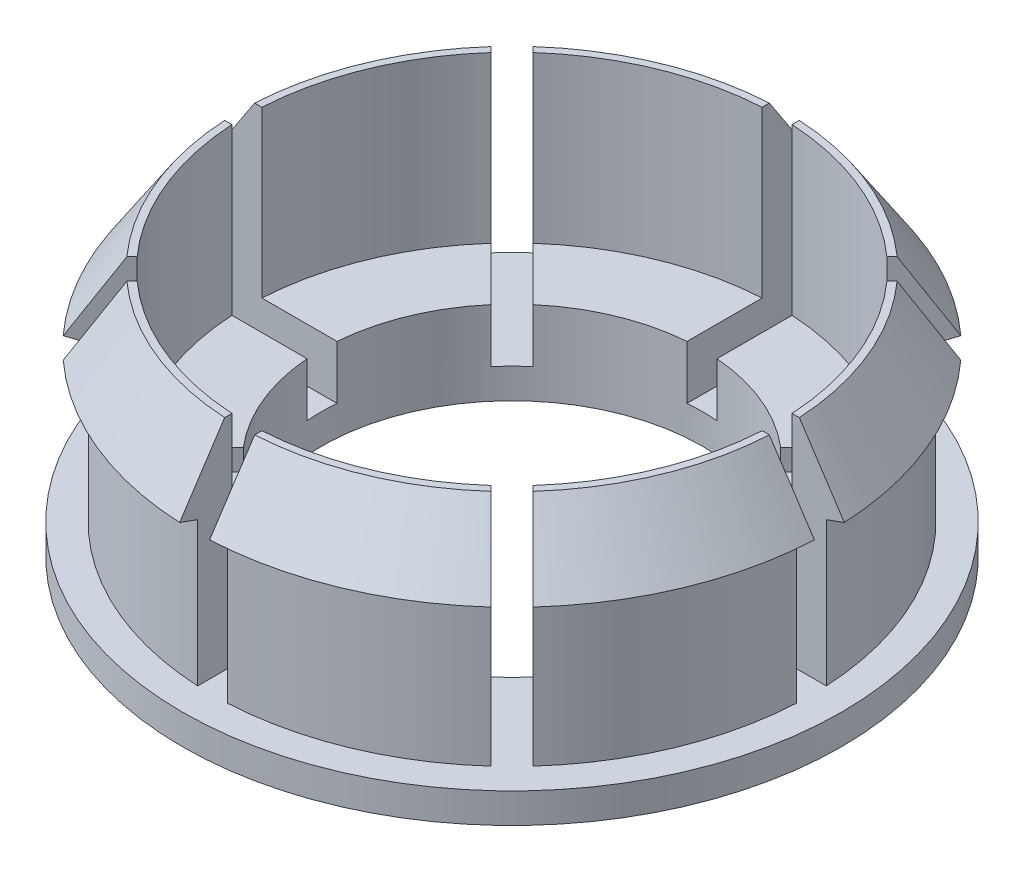
SolidWorks part; units mm, degrees
ref_plane "Front Plane" through (0, 0, 0) normal (0, 0, 1) x (1, 0, 0)
ref_plane "Top Plane" through (0, 0, 0) normal (0, 1, 0) x (1, 0, 0)
ref_plane "Right Plane" through (0, 0, 0) normal (1, 0, 0) x (0, 0, -1)
sketch "Sketch5" plane through (0, 0, 0) normal (0, 0, 1) x (1, 0, 0)
  line L0 (-11.25, -3.5) -> (-11.25, 3.5)
  line L1 (11.25, 3.5) -> (-11.25, 3.5) construction
  line L2 (11.25, 3.5) -> (11.25, -3.5) construction
  line L3 (11.25, -3.5) -> (-11.25, -3.5) construction
  line L4 (-11.25, 3.5) -> (-11.25, -3.5) construction
  line L5 (11.25, 3.5) -> (-11.25, -3.5) construction
  line L6 (11.25, -3.5) -> (-11.25, 3.5) construction
  line L7 (-11.25, 3.5) -> (-11.557, 3.5)
  line L8 (-11.557, 3.5) -> (-13.462, 0.6023)
  line L9 (-13.462, 0.6023) -> (-12.7, 0.325)
  line L10 (-12.7, 0.325) -> (-12.7, -5.775)
  line L11 (-12.7, -5.775) -> (-13.97, -5.775)
  line L12 (-13.97, -5.775) -> (-13.97, -7.045)
  line L13 (-13.97, -7.045) -> (-8.075, -7.045)
  line L14 (-8.075, -7.045) -> (-8.075, -3.5)
  line L15 (-8.075, -3.5) -> (-11.25, -3.5)
  line L16 (0, 0.325) -> (0, -8.827) construction
  line L17 (8.075, -7.045) -> (-8.075, -7.045) construction
  line L18 (8.075, -7.045) -> (8.075, -3.5) construction
  line L19 (8.075, -3.5) -> (-8.075, -3.5) construction
  line L20 (-8.075, -7.045) -> (-8.075, -3.5) construction
  line L21 (8.075, -7.045) -> (-8.075, -3.5) construction
  line L22 (8.075, -3.5) -> (-8.075, -7.045) construction
  line L23 (12.7, -5.775) -> (-12.7, -5.775) construction
  line L24 (12.7, -5.775) -> (12.7, 0.325) construction
  line L25 (12.7, 0.325) -> (-12.7, 0.325) construction
  line L26 (-12.7, -5.775) -> (-12.7, 0.325) construction
  line L27 (12.7, -5.775) -> (-12.7, 0.325) construction
  line L28 (12.7, 0.325) -> (-12.7, -5.775) construction
  point P0 (0, 0)
  point P7 (0, -5.2725)
  point P15 (-13.97, 0.7417)
  point P19 (0, -2.725)
  dimension "D1" = 7
  dimension "D2" = 22.5
  dimension "D3" = 3.175
  dimension "D4" = 6.1
  dimension "D5" = 3.175
  dimension "D6" = 25.4
  dimension "D7" = 0.762
  dimension "D8" = 1.905
  dimension "D9" = 1.27
  dimension "D10" = 1.27
  dimension "D11" = 70
revolve "Revolve1" add sketch "Sketch5" angle 360 about L16
sketch "Sketch6" plane through (0, 3.5, 0) normal (0, 1, 0) x (1, 0, 0)
  line L1 (0.635, 0) -> (-0.635, 0)
  line L2 (0.635, 0) -> (0.635, 13.462)
  line L3 (0.635, 13.462) -> (-0.635, 13.462)
  line L4 (-0.635, 0) -> (-0.635, 13.462)
  line L5 (0.635, 0) -> (-0.635, 13.462) construction
  line L6 (0.635, 13.462) -> (-0.635, 0) construction
  circle A0 centre (0, 0) radius 13.462 construction
  point P0 (0, 6.731)
  point P5 (0, 10.4053)
  point P6 (-0.9891, 10.5004)
  dimension "D1" = 1.27
extrude "Cut-Extrude3" cut sketch "Sketch6" against normal up to surface (9.275 mm away) and the other way through all up to face at (0, -5.775, 13.97)
ref_axis "Axis1" through (0, 4.0728, 0) along (0, -1, 0)
pattern_circular "CirPattern1" count 8 over 360 about axis through (0, 4.0728, 0) along (0, -1, 0) of "Cut-Extrude3"
